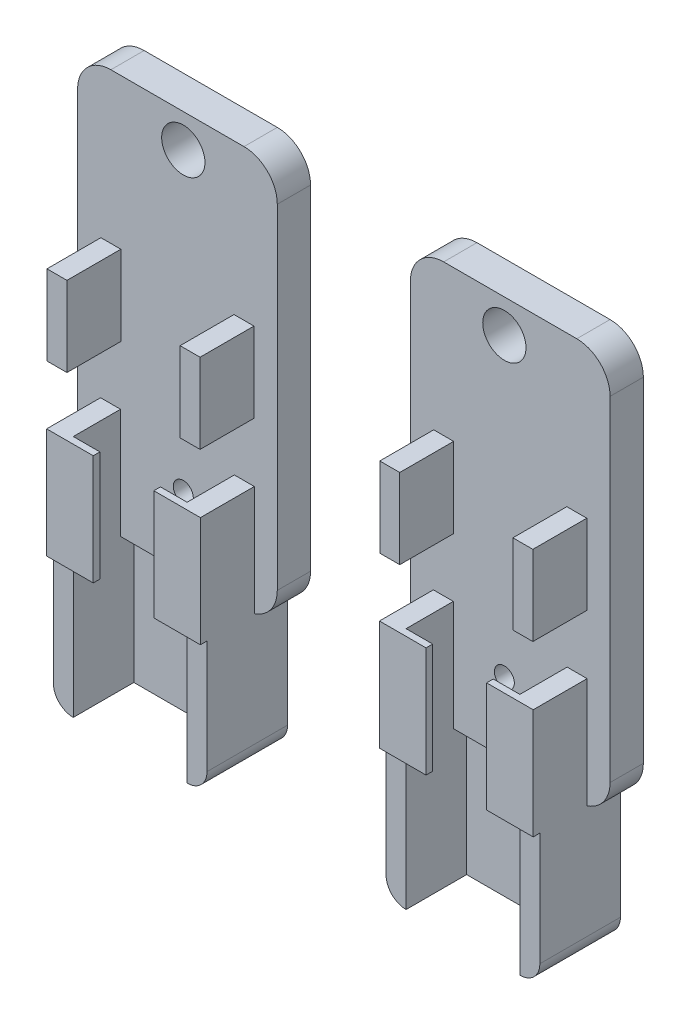
SolidWorks part; units mm, degrees
ref_plane "정면" through (0, 0, 0) normal (0, 0, 1) x (1, 0, 0)
ref_plane "윗면" through (0, 0, 0) normal (0, 1, 0) x (1, 0, 0)
ref_plane "우측면" through (0, 0, 0) normal (1, 0, 0) x (0, 0, -1)
sketch "스케치1" plane through (0, 0, 0) normal (0, 0, 1) x (1, 0, 0)
  line L5 (0, 0) -> (30, 0)
  line L6 (0, 0) -> (0, -60)
  line L7 (0, -60) -> (30, -60)
  line L8 (30, 0) -> (30, -60)
  circle A0 centre (15, -5) radius 2.1
  dimension "D4" = 4.2
  dimension "D2" = 5
  dimension "D1" = 30
  dimension "60" = 60
extrude "보스-돌출1" add sketch "스케치1" along normal blind 5 contours L6 L7 L8 L5
sketch "스케치2" plane through (0, 0, 5) normal (0, 0, 1) x (1, 0, 0)
  line L0 (15.88, -49.5) -> (15.88, 4.3374)
  line L1 (0, 0) -> (30, 0) construction
  line L3 (0, 0) -> (0, -60) construction
  circle A0 centre (15.88, -5) radius 3.25
  circle A1 centre (15.88, -49.5) radius 1.5
  dimension "D1" = 6.5
  dimension "D5" = 3
  dimension "D2" = 5
  dimension "D3" = 15.88
extrude "컷-돌출1" cut sketch "스케치2" against normal blind 10 contours A0 | A1
sketch "스케치3" plane through (0, 0, 5) normal (0, 0, 1) x (1, 0, 0)
  line L4 (0, -60) -> (30, -60) construction
  line L5 (6.45, -60) -> (3.45, -60)
  line L6 (6.45, -60) -> (6.45, -43.45)
  line L7 (6.45, -43.45) -> (3.45, -43.45)
  line L8 (3.45, -60) -> (3.45, -43.45)
  line L10 (23.55, -60) -> (26.5493, -60)
  line L11 (23.55, -60) -> (23.55, -43.45)
  line L12 (23.55, -43.45) -> (26.5493, -43.45)
  line L13 (26.5493, -60) -> (26.5493, -43.45)
  line L24 (6.5, -34.6022) -> (3.5, -34.6022)
  line L25 (6.5, -34.6022) -> (6.5, -22.6022)
  line L26 (6.5, -22.6022) -> (3.5, -22.6022)
  line L27 (3.5, -34.6022) -> (3.5, -22.6022)
  line L32 (23.5, -22.6022) -> (26.5, -22.6022)
  line L33 (23.5, -22.6022) -> (23.5, -34.6022)
  line L34 (23.5, -34.6022) -> (26.5, -34.6022)
  line L35 (26.5, -22.6022) -> (26.5, -34.6022)
  dimension "D3" = 16.55
  dimension "D4" = 3
  dimension "D5" = 2.9993
  dimension "D7" = 3
  dimension "D8" = 12
  dimension "D9" = 3
extrude "보스-돌출2" add sketch "스케치3" along normal blind 8.1
sketch "스케치4" plane through (6.45, 0, 0) normal (1, 0, 0) x (0, 0, -1)
  line L0 (-13.1, -60) -> (-5, -60) construction
  line L1 (-13.1, -43.45) -> (-12.1, -43.45)
  line L2 (-13.1, -43.45) -> (-13.1, -60)
  line L3 (-13.1, -60) -> (-12.1, -60)
  line L4 (-12.1, -43.45) -> (-12.1, -60)
  dimension "D1" = 1
extrude "보스-돌출3" add sketch "스케치4" along normal blind 4 contours L4 L3 L2 L1
sketch "스케치5" plane through (23.55, 0, 0) normal (-1, 0, 0) x (0, 0, 1)
  line L1 (13.1, -43.45) -> (12.1, -43.45)
  line L2 (13.1, -43.45) -> (13.1, -60)
  line L3 (13.1, -60) -> (12.1, -60)
  line L4 (12.1, -43.45) -> (12.1, -60)
extrude "보스-돌출4" add sketch "스케치5" along normal blind 4
sketch "스케치6" plane through (0, -60, 0) normal (0, -1, 0) x (1, 0, 0)
  line L0 (0, 0) -> (30, 0) construction
  line L1 (3.45, 0) -> (26.5493, 0)
  line L2 (3.45, 0) -> (3.45, 3)
  line L3 (6.45, 3) -> (23.55, 3)
  line L4 (26.5493, 0) -> (26.5493, 3)
  line L7 (3.45, 3) -> (3.45, 12.1)
  line L8 (3.45, 12.1) -> (6.45, 12.1)
  line L9 (6.45, 3) -> (6.45, 12.1)
  line L11 (26.5493, 3) -> (26.5493, 12.1)
  line L12 (26.5493, 12.1) -> (23.55, 12.1)
  line L13 (23.55, 3) -> (23.55, 12.1)
  dimension "D1" = 3
extrude "보스-돌출5" add sketch "스케치6" along normal blind 20
ref_plane "평면3" through (40, 0, 0) normal (1, 0, 0) x (0, 0, -1)
mirror "대칭 복사8" about plane through (40, 0, 0) normal (1, 0, 0) of bodies 110
fillet "필렛3" radius 5 4 edges at (30, -60, 2.5) (0, -60, 2.5) (30, 0, 2.5) (0, 0, 2.5)
fillet "필렛5" radius 3 2 edges at (3.45, -80, 6.05) (26.5493, -80, 6.05)
fillet "필렛6" radius 5 4 edges at (50, -60, 2.5) (80, -60, 2.5) (50, 0, 2.5) (80, 0, 2.5)
fillet "필렛7" radius 3 2 edges at (53.4507, -80, 6.05) (76.55, -80, 6.05)
